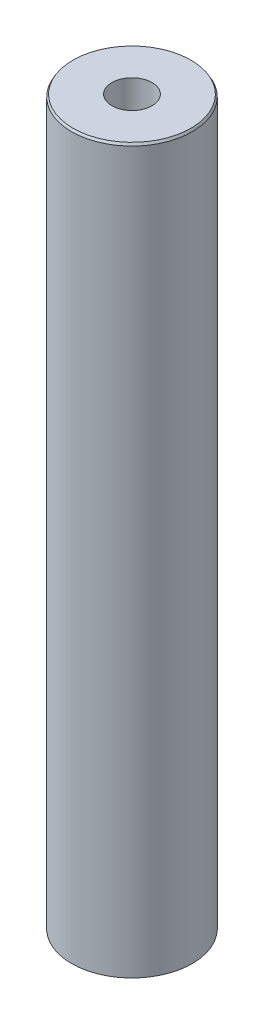
SolidWorks part; units mm, degrees
ref_plane "Front Plane" through (0, 0, 0) normal (0, 0, 1) x (1, 0, 0)
ref_plane "Top Plane" through (0, 0, 0) normal (0, 1, 0) x (1, 0, 0)
ref_plane "Right Plane" through (0, 0, 0) normal (1, 0, 0) x (0, 0, -1)
sketch "Sketch1" plane through (0, 0, 0) normal (0, 1, 0) x (1, 0, 0)
  circle A0 centre (0, 0) radius 50
  dimension "SHAFT_OD" = 100
extrude "Boss-Extrude1" add sketch "Sketch1" along normal blind 600
sketch "Sketch2" plane through (0, 0, 0) normal (0, 1, 0) x (1, 0, 0)
  circle A0 centre (0, 0) radius 16.6505
  dimension "BORE_D" = 33.3011
extrude "Cut-Extrude1" cut sketch "Sketch2" along normal through all
chamfer "Chamfer1" distance 1.9297 angle 30 2 edges at (0, 600, 50) (0, 0, 50) first distance on face at (0, 600, 50) first distance on face at (0, 0, 16.6505)
